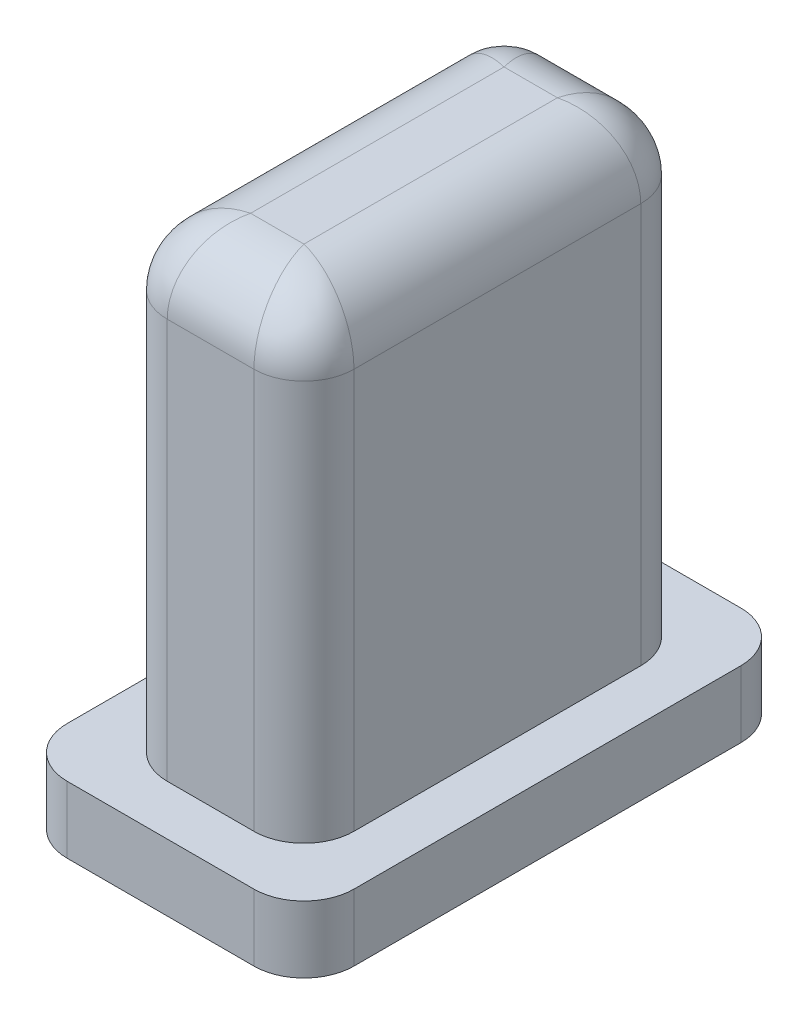
SolidWorks part; units mm, degrees
ref_plane "Front Plane" through (0, 0, 0) normal (0, 0, 1) x (1, 0, 0)
ref_plane "Top Plane" through (0, 0, 0) normal (0, 1, 0) x (1, 0, 0)
ref_plane "Right Plane" through (0, 0, 0) normal (1, 0, 0) x (0, 0, -1)
sketch "Sketch1" plane through (0, 0, 0) normal (0, 1, 0) x (1, 0, 0)
  line L1 (0, 0) -> (-2.8, 0)
  line L2 (0, 0) -> (0, -5.8)
  line L3 (0, -5.8) -> (-2.8, -5.8)
  line L4 (-2.8, 0) -> (-2.8, -5.8)
  dimension "D1" = 5.8
  dimension "D2" = 2.8
extrude "Boss-Extrude1" add sketch "Sketch1" along normal blind 7
sketch "Sketch2" plane through (0, 0, 0) normal (0, -1, 0) x (1, 0, 0)
  line L0 (0, 5.8) -> (0, 0) construction
  line L1 (0.75, -0.75) -> (-3.55, -0.75)
  line L2 (0.75, -0.75) -> (0.75, 6.55)
  line L3 (0.75, 6.55) -> (-3.55, 6.55)
  line L4 (-3.55, -0.75) -> (-3.55, 6.55)
  line L5 (-2.8, 5.8) -> (0, 5.8) construction
  line L6 (-2.8, 0) -> (-2.8, 5.8) construction
  line L7 (0, 0) -> (-2.8, 0) construction
  dimension "D1" = 0.75
  dimension "D2" = 0.75
  dimension "D3" = 0.75
  dimension "D4" = 0.75
extrude "Boss-Extrude2" add sketch "Sketch2" along normal blind 1
fillet "Fillet1" radius 0.75 8 edges at (0.75, -0.5, -0.75) (0.75, -0.5, 6.55) (0, 3.5, 5.8) (0, 3.5, 0) (-3.55, -0.5, -0.75) (-3.55, -0.5, 6.55) (-2.8, 3.5, 5.8) (-2.8, 3.5, 0)
fillet "Fillet2" radius 1 8 edges at (-2.5803, 7, 5.5803) (-2.8, 7, 2.9) (-2.5803, 7, 0.2197) (-1.4, 7, 0) (-0.2197, 7, 0.2197) (0, 7, 2.9) (-0.2197, 7, 5.5803) (-1.4, 7, 5.8)
